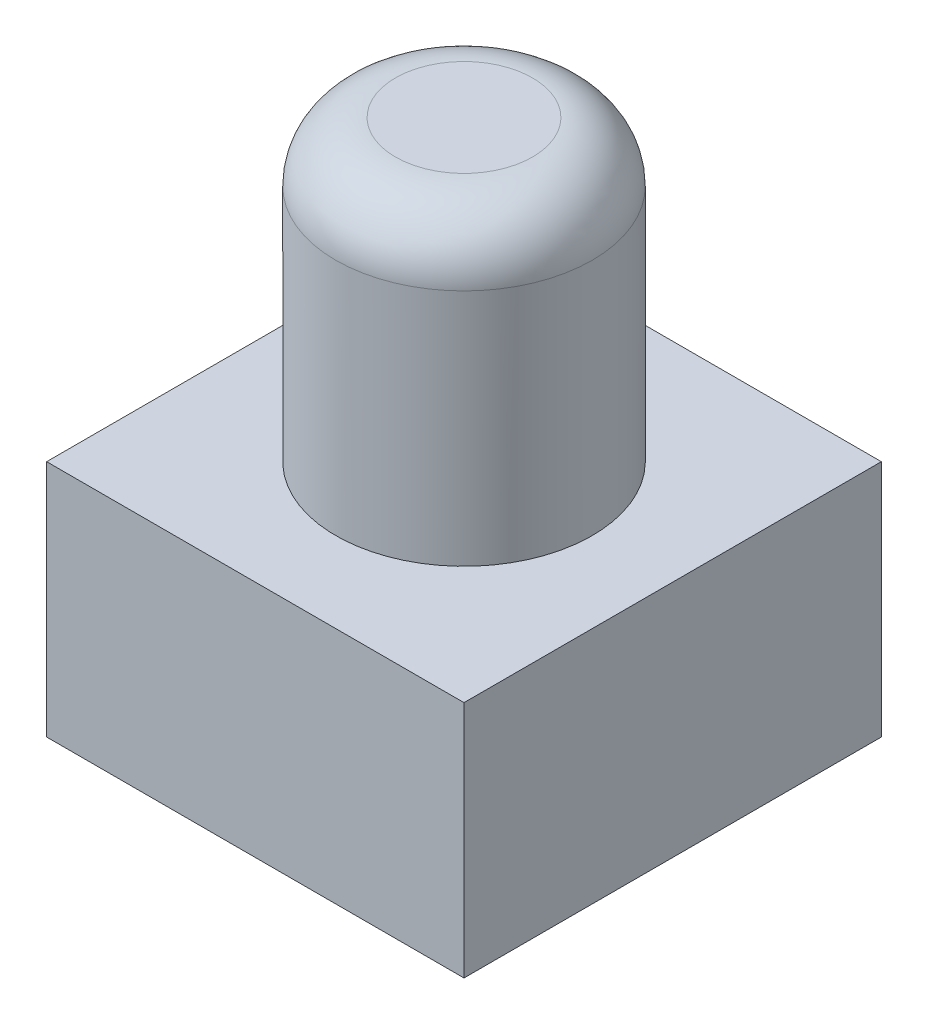
SolidWorks part; units mm, degrees
ref_plane "Front Plane" through (0, 0, 0) normal (0, 0, 1) x (1, 0, 0)
ref_plane "Top Plane" through (0, 0, 0) normal (0, 1, 0) x (1, 0, 0)
ref_plane "Right Plane" through (0, 0, 0) normal (1, 0, 0) x (0, 0, -1)
sketch "Sketch1" plane through (0, 0, 0) normal (0, 1, 0) x (1, 0, 0)
  circle A0 centre (0, 0) radius 2.15
  dimension "D1" = 4.3
extrude "Boss-Extrude1" add sketch "Sketch1" along normal blind 7
sketch "Sketch3" plane through (0, 0, 0) normal (0, -1, 0) x (1, 0, 0)
  line L1 (-3.5, 3.5) -> (3.5, 3.5)
  line L2 (-3.5, 3.5) -> (-3.5, -3.5)
  line L3 (-3.5, -3.5) -> (3.5, -3.5)
  line L4 (3.5, 3.5) -> (3.5, -3.5)
  line L5 (-3.5, 3.5) -> (3.5, -3.5) construction
  line L6 (-3.5, -3.5) -> (3.5, 3.5) construction
  point P0 (0, 0)
  dimension "D1" = 7
extrude "Boss-Extrude2" add sketch "Sketch3" against normal blind 2 and the other way blind 2
fillet "Fillet1" radius 1 1 edges at (0, 7, 2.15)
sketch "Sketch5" plane through (0, -2, 0) normal (0, -1, 0) x (1, 0, 0)
  line L1 (-2.75, 2.75) -> (2.75, 2.75)
  line L2 (-2.75, 2.75) -> (-2.75, -2.75)
  line L3 (-2.75, -2.75) -> (2.75, -2.75)
  line L4 (2.75, 2.75) -> (2.75, -2.75)
  dimension "D1" = 5.5
extrude "Cut-Extrude1" cut sketch "Sketch5" against normal blind 2
